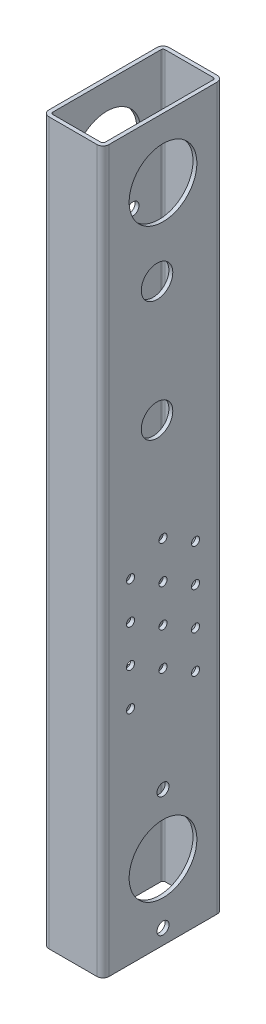
SolidWorks part; units mm, degrees
material "6061-T6 (SS)"
ref_plane "Front Plane" through (0, 0, 0) normal (0, 0, 1) x (1, 0, 0)
ref_plane "Top Plane" through (0, 0, 0) normal (0, 1, 0) x (1, 0, 0)
ref_plane "Right Plane" through (0, 0, 0) normal (1, 0, 0) x (0, 0, -1)
sketch "Sketch1" plane through (0, 0, 0) normal (0, 1, 0) x (1, 0, 0)
  line L1 (10.16, -25.4) -> (-10.16, -25.4)
  line L2 (12.7, -22.86) -> (12.7, 22.86)
  line L3 (10.16, 25.4) -> (-10.16, 25.4)
  line L4 (-12.7, -22.86) -> (-12.7, 22.86)
  line L5 (12.7, -25.4) -> (-12.7, 25.4) construction
  line L6 (12.7, 25.4) -> (-12.7, -25.4) construction
  arc A0 (-10.16, -25.4) -> (-12.7, -22.86) centre (-10.16, -22.86) cw
  arc A1 (10.16, -25.4) -> (12.7, -22.86) centre (10.16, -22.86) ccw
  arc A2 (12.7, 22.86) -> (10.16, 25.4) centre (10.16, 22.86) ccw
  arc A3 (-10.16, 25.4) -> (-12.7, 22.86) centre (-10.16, 22.86) ccw
  point P0 (0, 0)
  dimension "D3" = 2.54
  dimension "D1" = 25.4
  dimension "D2" = 50.8
extrude "Extrude-Thin1" add sketch "Sketch1" along normal blind 222.25 and the other way blind 82.55 thin thin type one direction reverse wall 1.651
sketch "Sketch2" plane through (-12.7, 0, 0) normal (-1, 0, 0) x (0, 0, 1)
  line L0 (2.54, 161.9426) -> (2.54, 12.7) construction
  line L4 (9.2075, 161.9426) -> (9.2075, 12.7)
  line L5 (-4.1275, 161.9426) -> (-4.1275, 12.7)
  line L6 (2.54, 25.4) -> (2.54, 149.2426) construction
  arc A2 (9.2075, 161.9426) -> (-4.1275, 161.9426) centre (2.54, 161.9426) ccw
  arc A3 (-4.1275, 12.7) -> (9.2075, 12.7) centre (2.54, 12.7) ccw
  point P3 (2.54, 87.3213)
  dimension "D5" = 13.335
  dimension "D2" = 12.7
  dimension "D1" = 12.7
extrude "Cut-Extrude1" cut sketch "Sketch2" against normal up to next
sketch "Sketch5" plane through (12.7, 0, 0) normal (1, 0, 0) x (0, 0, -1)
  circle A3 centre (-2.54, 111.1426) radius 6.6675 construction
  circle A4 centre (-2.54, 111.1426) radius 6.6675
  circle A5 centre (-2.54, 161.9426) radius 6.6675 construction
  circle A6 centre (-2.54, 161.9426) radius 6.6675
extrude "Cut-Extrude4" cut sketch "Sketch5" against normal up to next
sketch "Sketch4" plane through (-12.7, 0, 0) normal (1, 0, 0) x (0, 0, -1)
  circle A12 centre (11.049, 4.7713) radius 2.5527
  circle A13 centre (-16.129, 4.7713) radius 2.5527
  circle A14 centre (-16.129, 87.3213) radius 2.5527
  circle A15 centre (11.049, 87.3213) radius 2.5527
  circle A16 centre (-16.129, 169.8713) radius 2.5527
  circle A17 centre (11.049, 169.8713) radius 2.5527
  dimension "D1" = 5.1054
extrude "Cut-Extrude3" cut sketch "Sketch4" along normal up to surface (1.651 mm away) up to face at (-11.049, 87.3213, 2.54)
sketch "Sketch6" plane through (12.7, 0, 0) normal (1, 0, 0) x (0, 0, -1)
  line L0 (25.4, -82.55) -> (25.4, 222.25) construction
  circle A0 centre (0, -50.8) radius 14.3256
  circle A1 centre (0, 196.85) radius 14.3256
  dimension "D1" = 28.6512
  dimension "D2" = 25.4
  dimension "D3" = 50.8
  dimension "D4" = 247.65
extrude "Cut-Extrude5" cut sketch "Sketch6" against normal through all
hole_wizard "#10 Clearance Hole1" positions "Sketch8" profile "Sketch9" hole size "#10" standard "ANSI Inch" end condition through all
sketch "Sketch8" plane through (12.7, 0, 0) normal (1, 0, 0) x (0, 0, -1)
  circle A0 centre (0, -50.8) radius 25.4 construction
  point P0 (0, -25.4)
  point P11 (0, -76.2)
  dimension "D1" = 50.8
sketch "Sketch9" plane through (12.7, -25.4, 0) normal (0, 1, 0) x (0, 0, -1)
  line L0 (0, 0) -> (0, 25.4)
  line L1 (0, 25.4) -> (2.5527, 25.4)
  line L2 (2.5527, 25.4) -> (2.5527, 0)
  line L5 (2.5527, 0) -> (0, 0)
  line L11 (0, -6.35) -> (0, 107.95) construction
  dimension "Thru Hole Dia." = 5.1054
  dimension "Thru Hole Depth" = 25.4
hole_wizard "1/8 (0.135) Diameter Hole1" positions "Sketch10" profile "Sketch11" hole size "1/8" standard "ANSI Inch" end condition up to next
sketch "Sketch10" plane through (12.7, 0, 0) normal (1, 0, 0) x (0, 0, -1)
  point P0 (0, 66.5303)
  point P3 (13.7482, 58.5928)
  point P8 (-13.7482, 58.5928)
  point P11 (-13.7482, 42.7178)
  point P14 (13.7482, 42.7178)
  point P17 (0, 34.7803)
  point P20 (-13.7482, 26.8428)
  point P23 (13.7482, 26.8428)
  point P26 (0, 18.9053)
  point P29 (13.7482, 10.9678)
  point P32 (-13.7482, 10.9678)
  point P35 (0, 50.6553)
sketch "Sketch11" plane through (12.7, 66.5303, 0) normal (0, 1, 0) x (0, 0, -1)
  line L0 (0, 0) -> (0, 1.651)
  line L1 (0, 1.651) -> (1.7145, 1.651)
  line L2 (1.7145, 1.651) -> (1.7145, 0)
  line L5 (1.7145, 0) -> (0, 0)
  line L11 (0, -6.35) -> (0, 107.95) construction
  dimension "Thru Hole Dia." = 3.429
  dimension "Thru Hole Depth" = 1.651
hole_wizard "1/8 (0.135) Diameter Hole2" positions "Sketch12" profile "Sketch13" hole size "1/8" standard "ANSI Inch" end condition up to next
sketch "Sketch12" plane through (-12.7, 0, 0) normal (-1, 0, 0) x (0, 0, 1)
  point P0 (17.399, 63.3553)
  point P3 (17.399, 53.8303)
  point P6 (17.399, 44.3053)
  point P9 (17.399, 34.7803)
  point P12 (17.399, 25.2553)
  point P15 (17.399, 15.7303)
sketch "Sketch13" plane through (-12.7, 63.3553, 17.399) normal (0, 1, 0) x (0, 0, 1)
  line L0 (0, 0) -> (0, 1.651)
  line L1 (0, 1.651) -> (1.7145, 1.651)
  line L2 (1.7145, 1.651) -> (1.7145, 0)
  line L5 (1.7145, 0) -> (0, 0)
  line L11 (0, -6.35) -> (0, 107.95) construction
  dimension "Thru Hole Dia." = 3.429
  dimension "Thru Hole Depth" = 1.651
move or copy body "Body-Move/Copy1" [suppressed] bodies to move or copy 110 parameters "D1"=0, "D2"=0, "D3"=0
